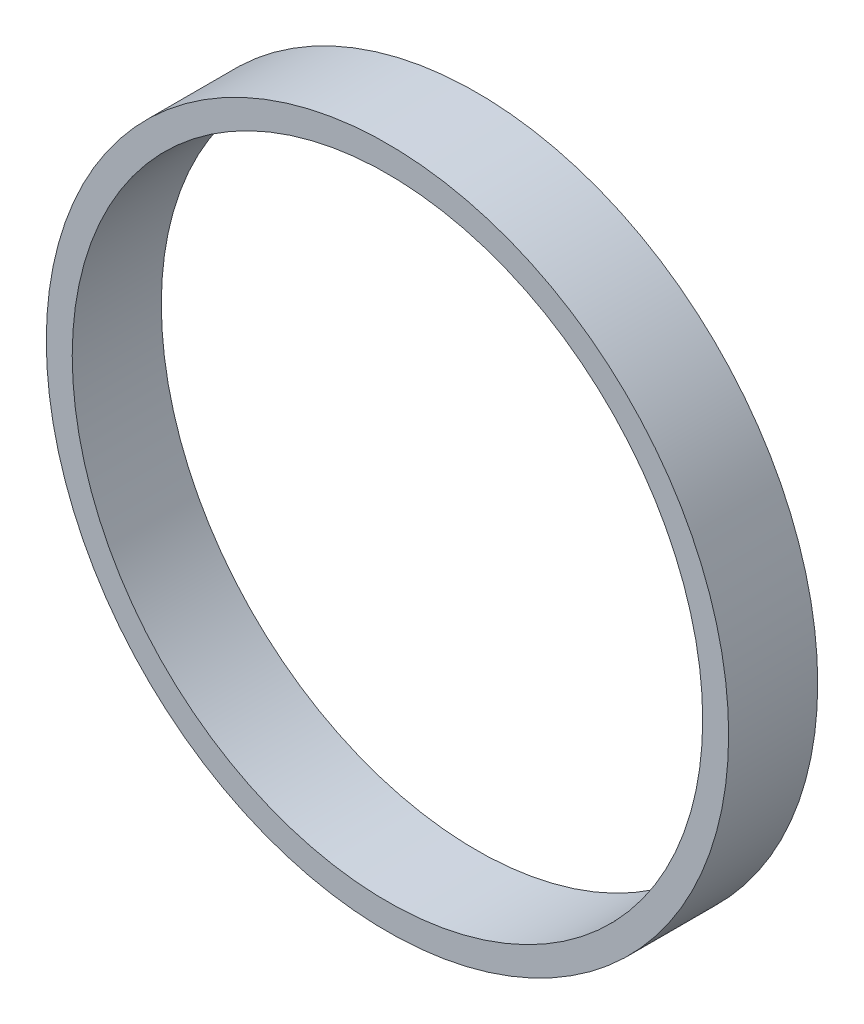
SolidWorks part; units mm, degrees
ref_plane "Front Plane" through (0, 0, 0) normal (0, 0, 1) x (1, 0, 0)
ref_plane "Top Plane" through (0, 0, 0) normal (0, 1, 0) x (1, 0, 0)
ref_plane "Right Plane" through (0, 0, 0) normal (1, 0, 0) x (0, 0, -1)
ref_axis "X-Axis" through (-88.99, 0, 0) along (1, 0, 0)
ref_axis "Y-Axis" through (0, 55, 0) along (0, -1, 0)
ref_axis "Z-Axis" through (0, 0, -88.99) along (0, 0, 1)
sketch "Sketch1" plane through (0, 0, 0) normal (0, 0, 1) x (1, 0, 0)
  circle A0 centre (0, 0) radius 72.9
  circle A1 centre (0, 0) radius 78.9
  dimension "D1" = 145.8
  dimension "D2" = 157.8
extrude "Boss-Extrude1" add sketch "Sketch1" along normal mid plane 20.6
equation "\"D2@Sketch1\"=\"D1@Sketch1\"+(6*2)"
